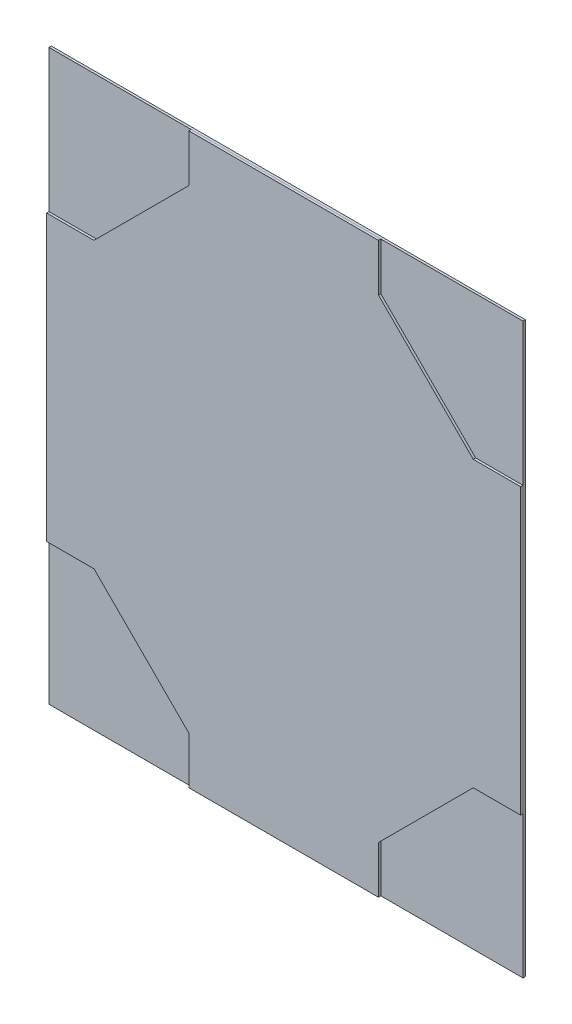
SolidWorks part; units mm, degrees
ref_plane "Front Plane" through (0, 0, 0) normal (0, 0, 1) x (1, 0, 0)
ref_plane "Top Plane" through (0, 0, 0) normal (0, 1, 0) x (1, 0, 0)
ref_plane "Right Plane" through (0, 0, 0) normal (1, 0, 0) x (0, 0, -1)
sketch "Sketch1" plane through (0, 0, 0) normal (0, 0, 1) x (1, 0, 0)
  line L1 (-317.5, 381) -> (317.5, 381)
  line L2 (-317.5, 381) -> (-317.5, -381)
  line L3 (-317.5, -381) -> (317.5, -381)
  line L4 (317.5, 381) -> (317.5, -381)
  line L5 (-317.5, 381) -> (317.5, -381) construction
  line L6 (-317.5, -381) -> (317.5, 381) construction
  point P0 (0, 0)
  dimension "D1" = 762
  dimension "D2" = 635
extrude "Boss-Extrude1" add sketch "Sketch1" along normal blind 3.175
sketch "Sketch3" plane through (0, 0, 3.175) normal (0, 0, 1) x (1, 0, 0)
  line L0 (-127, 381) -> (127, 381)
  line L2 (317.5, 381) -> (-317.5, 381) construction
  line L3 (-317.5, 190.5) -> (-317.5, -190.5)
  line L5 (-317.5, 381) -> (-317.5, -381) construction
  line L6 (317.5, 190.5) -> (317.5, -190.5)
  line L7 (317.5, -381) -> (317.5, 381) construction
  line L8 (-127, -381) -> (127, -381)
  line L9 (-317.5, -381) -> (317.5, -381) construction
  line L10 (-317.5, 190.5) -> (-254, 190.5)
  line L11 (-127, 381) -> (-127, 317.5)
  line L12 (-317.5, -190.5) -> (-254, -190.5)
  line L13 (-127, -381) -> (-127, -317.5)
  line L14 (127, 381) -> (127, 317.5)
  line L15 (317.5, 190.5) -> (254, 190.5)
  line L16 (317.5, -190.5) -> (254, -190.5)
  line L17 (127, -381) -> (127, -317.5)
  line L18 (127, -317.5) -> (254, -190.5)
  line L19 (-254, -190.5) -> (-127, -317.5)
  line L20 (-254, 190.5) -> (-127, 317.5)
  line L21 (127, 317.5) -> (254, 190.5)
  point P5 (0, 381)
  point P10 (-317.5, 0)
  point P15 (317.5, 0)
  point P20 (0, -381)
  dimension "D1" = 63.5
  dimension "D2" = 63.5
  dimension "D3" = 63.5
  dimension "D4" = 63.5
  dimension "D5" = 63.5
  dimension "D6" = 63.5
  dimension "D7" = 63.5
  dimension "D8" = 63.5
  dimension "D9" = 381
extrude "Boss-Extrude2" add sketch "Sketch3" along normal blind 3.175 separate body
